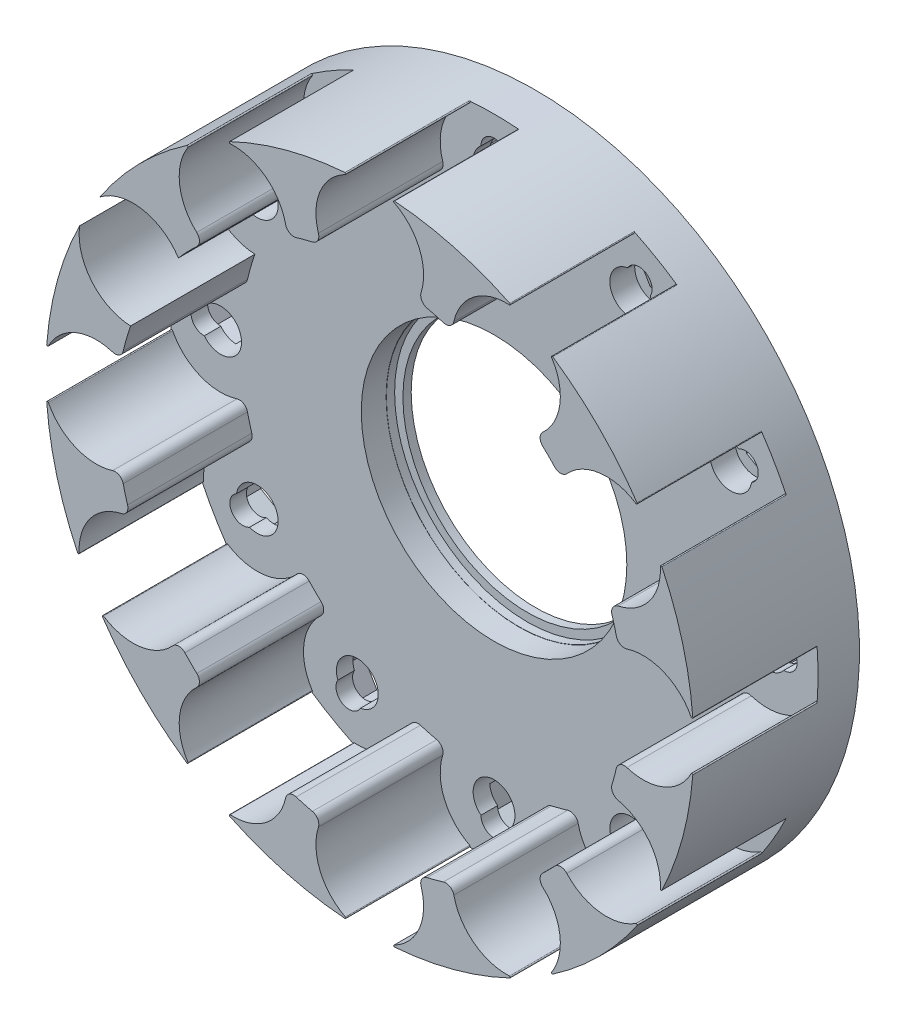
SolidWorks part; units mm, degrees
material "ABS"
ref_plane "Front Plane" through (0, 0, 0) normal (0, 0, 1) x (1, 0, 0)
ref_plane "Top Plane" through (0, 0, 0) normal (0, 1, 0) x (1, 0, 0)
ref_plane "Right Plane" through (0, 0, 0) normal (1, 0, 0) x (0, 0, -1)
sketch "Sketch1" plane through (0, 0, 0) normal (0, 0, 1) x (1, 0, 0)
  circle A0 centre (0, 0) radius 39.1
  circle A1 centre (0, 0) radius 33 construction
  circle A2 centre (33, 0) radius 2.525
  circle A3 centre (28.5788, -16.5) radius 2.525
  circle A4 centre (16.5, -28.5788) radius 2.525
  circle A5 centre (0, -33) radius 2.525
  circle A6 centre (-16.5, -28.5788) radius 2.525
  circle A7 centre (-28.5788, -16.5) radius 2.525
  circle A8 centre (-33, 0) radius 2.525
  circle A9 centre (-28.5788, 16.5) radius 2.525
  circle A10 centre (-16.5, 28.5788) radius 2.525
  circle A11 centre (0, 33) radius 2.525
  circle A12 centre (16.5, 28.5788) radius 2.525
  circle A13 centre (0, 0) radius 16.025
  circle A14 centre (28.5788, 16.5) radius 2.525
  point P28 (0, 0)
extrude "Boss-Extrude1" add sketch "Sketch1" along normal blind 3
sketch "Sketch2" plane through (0, 0, 0) normal (0, 0, -1) x (-1, 0, 0)
  circle A0 centre (0, 0) radius 16
  circle A1 centre (0, 0) radius 39.1
  circle A2 centre (0, 0) radius 39.1 construction
  dimension "D1" = 32
extrude "Boss-Extrude2" add sketch "Sketch2" along normal blind 2 contours A1 | A0
sketch "Sketch3" plane through (0, 0, 3) normal (0, 0, 1) x (1, 0, 0)
  circle A0 centre (33, 0) radius 1.6
  circle A1 centre (28.5788, -16.5) radius 1.6
  circle A2 centre (16.5, -28.5788) radius 1.6
  circle A3 centre (0, -33) radius 1.6
  circle A4 centre (-16.5, -28.5788) radius 1.6
  circle A5 centre (-28.5788, -16.5) radius 1.6
  circle A6 centre (-33, 0) radius 1.6
  circle A7 centre (-28.5788, 16.5) radius 1.6
  circle A8 centre (-16.5, 28.5788) radius 1.6
  circle A9 centre (0, 33) radius 1.6
  circle A10 centre (16.5, 28.5788) radius 1.6
  circle A11 centre (28.5788, 16.5) radius 1.6
  point P25 (0, 0)
  dimension "D1" = 3.2
  dimension "D2" = 12
sketch "Sketch4" plane through (0, 0, -2) normal (0, 0, -1) x (-1, 0, 0)
  circle A0 centre (0, 0) radius 16
  circle A1 centre (0, 0) radius 15
  dimension "D1" = 32
  dimension "D2" = 30
extrude "Boss-Extrude3" add sketch "Sketch4" against normal blind 1
sketch "Sketch5" plane through (0, 0, 3) normal (0, 0, 1) x (1, 0, 0)
  circle A0 centre (0, 0) radius 39.1
  circle A1 centre (0, 0) radius 39.1 construction
  arc A2 (-10.0063, 28.8658) -> (-19.9953, 23.0986) centre (-16.5, 28.5788) ccw
  arc A3 (5.7671, 30.0016) -> (-5.7671, 30.0016) centre (0, 33) ccw
  arc A4 (19.9953, 23.0986) -> (10.0063, 28.8658) centre (16.5, 28.5788) ccw
  arc A5 (28.8658, 10.0063) -> (23.0986, 19.9953) centre (28.5788, 16.5) ccw
  arc A6 (30.0016, -5.7671) -> (30.0016, 5.7671) centre (33, 0) ccw
  arc A7 (23.0986, -19.9953) -> (28.8658, -10.0063) centre (28.5788, -16.5) ccw
  arc A8 (10.0063, -28.8658) -> (19.9953, -23.0986) centre (16.5, -28.5788) ccw
  arc A9 (-5.7671, -30.0016) -> (5.7671, -30.0016) centre (0, -33) ccw
  arc A10 (-19.9953, -23.0986) -> (-10.0063, -28.8658) centre (-16.5, -28.5788) ccw
  arc A11 (-28.8658, -10.0063) -> (-23.0986, -19.9953) centre (-28.5788, -16.5) ccw
  arc A12 (-30.0016, 5.7671) -> (-30.0016, -5.7671) centre (-33, 0) ccw
  arc A13 (-23.0986, -19.9953) -> (-19.9953, -23.0986) centre (0, 0) ccw
  arc A14 (-30.0016, -5.7671) -> (-28.8658, -10.0063) centre (0, 0) ccw
  arc A15 (-19.9953, 23.0986) -> (-30.0016, 5.7671) centre (0, 0) ccw
  arc A16 (-5.7671, 30.0016) -> (-10.0063, 28.8658) centre (0, 0) ccw
  arc A17 (10.0063, 28.8658) -> (5.7671, 30.0016) centre (0, 0) ccw
  arc A18 (23.0986, 19.9953) -> (19.9953, 23.0986) centre (0, 0) ccw
  arc A19 (30.0016, 5.7671) -> (28.8658, 10.0063) centre (0, 0) ccw
  arc A20 (28.8658, -10.0063) -> (30.0016, -5.7671) centre (0, 0) ccw
  arc A21 (19.9953, -23.0986) -> (23.0986, -19.9953) centre (0, 0) ccw
  arc A22 (5.7671, -30.0016) -> (10.0063, -28.8658) centre (0, 0) ccw
  arc A23 (-10.0063, -28.8658) -> (-5.7671, -30.0016) centre (0, 0) ccw
  arc A24 (-23.0986, 19.9953) -> (-28.8658, 10.0063) centre (-28.5788, 16.5) ccw
  point P30 (0, 0)
  dimension "D1" = 12
  dimension "D2" = 6.5
extrude "Boss-Extrude4" add sketch "Sketch5" along normal blind 15 contours A24 A15 A2 A0 | A16 A3 A0 A2 | A17 A4 A0 A3 | A18 A5 A0 A4 | A19 A6 A0 A5 | A20 A7 A0 A6 | A21 A8 A0 A7 | A22 A9 A0 A8 | A23 A10 A0 A9 | A13 A11 A0 A10 | A14 A12 A0 A11 | A24 A0 A12 A15 region at (34.5325, 9.253, 3) region at (34.5325, -9.253, 3) region at (25.2796, 25.2796, 3) region at (25.2796, -25.2796, 3) region at (9.253, 34.5325, 3) region at (9.253, -34.5325, 3) region at (-9.253, 34.5325, 3) region at (-9.253, -34.5325, 3) region at (-25.2796, 25.2796, 3) region at (-25.2796, -25.2796, 3) region at (-34.5325, 9.253, 3) region at (-34.5325, -9.253, 3)
fillet "Fillet1" radius 0.1 22 edges at (-21.6271, 32.5742, 10.5) (-39.0236, -2.4425, 10.5) (-39.0236, 2.4425, 10.5) (-35.0167, -17.3966, 10.5) (-32.5742, -21.6271, 10.5) (-21.6271, -32.5742, 10.5) (-17.3966, -35.0167, 10.5) (-2.4425, -39.0236, 10.5) (2.4425, -39.0236, 10.5) (17.3966, -35.0167, 10.5) (21.6271, -32.5742, 10.5) (32.5742, -21.6271, 10.5) (35.0167, -17.3966, 10.5) (39.0236, -2.4425, 10.5) (39.0236, 2.4425, 10.5) (35.0167, 17.3966, 10.5) (21.6271, 32.5742, 10.5) (32.5742, 21.6271, 10.5) (17.3966, 35.0167, 10.5) (2.4425, 39.0236, 10.5) (-2.4425, 39.0236, 10.5) (-17.3966, 35.0167, 10.5)
fillet "Fillet2" radius 1 22 edges at (10.0063, -28.8658, 10.5) (5.7671, -30.0016, 10.5) (30.0016, -5.7671, 10.5) (28.8658, -10.0063, 10.5) (23.0986, -19.9953, 10.5) (19.9953, -23.0986, 10.5) (-10.0063, -28.8658, 10.5) (-5.7671, -30.0016, 10.5) (-19.9953, -23.0986, 10.5) (-23.0986, -19.9953, 10.5) (-30.0016, -5.7671, 10.5) (-28.8658, -10.0063, 10.5) (-30.0016, 5.7671, 10.5) (-19.9953, 23.0986, 10.5) (30.0016, 5.7671, 10.5) (28.8658, 10.0063, 10.5) (23.0986, 19.9953, 10.5) (19.9953, 23.0986, 10.5) (10.0063, 28.8658, 10.5) (5.7671, 30.0016, 10.5) (-5.7671, 30.0016, 10.5) (-10.0063, 28.8658, 10.5)
sketch "Sketch7" plane through (0, 0, -2) normal (0, 0, -1) x (-1, 0, 0)
  line L0 (0, 0) -> (35, 0) construction
  circle A0 centre (35, 0) radius 1.575
  circle A1 centre (30.3109, -17.5) radius 1.575
  circle A2 centre (17.5, -30.3109) radius 1.575
  circle A3 centre (0, -35) radius 1.575
  circle A4 centre (-17.5, -30.3109) radius 1.575
  circle A5 centre (-30.3109, -17.5) radius 1.575
  circle A6 centre (-35, 0) radius 1.575
  circle A7 centre (-30.3109, 17.5) radius 1.575
  circle A8 centre (-17.5, 30.3109) radius 1.575
  circle A9 centre (0, 35) radius 1.575
  circle A10 centre (17.5, 30.3109) radius 1.575
  circle A11 centre (30.3109, 17.5) radius 1.575
  point P26 (0, 0)
  dimension "D2" = 3.15
  dimension "D1" = 35
  dimension "D3" = 12
extrude "Cut-Extrude1" cut sketch "Sketch7" against normal through all
sketch "Sketch8" plane through (0, 0, -2) normal (0, 0, -1) x (-1, 0, 0)
  line L0 (33.1609, -19.1454) -> (33.1609, -15.8546)
  line L1 (38.2909, 0) -> (36.6454, 2.85)
  line L2 (36.6454, 2.85) -> (33.3546, 2.85)
  line L3 (33.3546, 2.85) -> (31.7091, 0)
  line L4 (31.7091, 0) -> (33.3546, -2.85)
  line L5 (33.3546, -2.85) -> (36.6454, -2.85)
  line L6 (36.6454, -2.85) -> (38.2909, 0)
  line L7 (33.1609, -15.8546) -> (30.3109, -14.2091)
  line L8 (30.3109, -14.2091) -> (27.4609, -15.8546)
  line L9 (27.4609, -15.8546) -> (27.4609, -19.1454)
  line L10 (27.4609, -19.1454) -> (30.3109, -20.7909)
  line L11 (30.3109, -20.7909) -> (33.1609, -19.1454)
  line L12 (19.1454, -33.1609) -> (20.7909, -30.3109)
  line L13 (20.7909, -30.3109) -> (19.1454, -27.4609)
  line L14 (19.1454, -27.4609) -> (15.8546, -27.4609)
  line L15 (15.8546, -27.4609) -> (14.2091, -30.3109)
  line L16 (14.2091, -30.3109) -> (15.8546, -33.1609)
  line L17 (15.8546, -33.1609) -> (19.1454, -33.1609)
  line L18 (0, -38.2909) -> (2.85, -36.6454)
  line L19 (2.85, -36.6454) -> (2.85, -33.3546)
  line L20 (2.85, -33.3546) -> (0, -31.7091)
  line L21 (0, -31.7091) -> (-2.85, -33.3546)
  line L22 (-2.85, -33.3546) -> (-2.85, -36.6454)
  line L23 (-2.85, -36.6454) -> (0, -38.2909)
  line L24 (-19.1454, -33.1609) -> (-15.8546, -33.1609)
  line L25 (-15.8546, -33.1609) -> (-14.2091, -30.3109)
  line L26 (-14.2091, -30.3109) -> (-15.8546, -27.4609)
  line L27 (-15.8546, -27.4609) -> (-19.1454, -27.4609)
  line L28 (-19.1454, -27.4609) -> (-20.7909, -30.3109)
  line L29 (-20.7909, -30.3109) -> (-19.1454, -33.1609)
  line L30 (-33.1609, -19.1454) -> (-30.3109, -20.7909)
  line L31 (-30.3109, -20.7909) -> (-27.4609, -19.1454)
  line L32 (-27.4609, -19.1454) -> (-27.4609, -15.8546)
  line L33 (-27.4609, -15.8546) -> (-30.3109, -14.2091)
  line L34 (-30.3109, -14.2091) -> (-33.1609, -15.8546)
  line L35 (-33.1609, -15.8546) -> (-33.1609, -19.1454)
  line L36 (-38.2909, 0) -> (-36.6454, -2.85)
  line L37 (-36.6454, -2.85) -> (-33.3546, -2.85)
  line L38 (-33.3546, -2.85) -> (-31.7091, 0)
  line L39 (-31.7091, 0) -> (-33.3546, 2.85)
  line L40 (-33.3546, 2.85) -> (-36.6454, 2.85)
  line L41 (-36.6454, 2.85) -> (-38.2909, 0)
  line L42 (-33.1609, 19.1454) -> (-33.1609, 15.8546)
  line L43 (-33.1609, 15.8546) -> (-30.3109, 14.2091)
  line L44 (-30.3109, 14.2091) -> (-27.4609, 15.8546)
  line L45 (-27.4609, 15.8546) -> (-27.4609, 19.1454)
  line L46 (-27.4609, 19.1454) -> (-30.3109, 20.7909)
  line L47 (-30.3109, 20.7909) -> (-33.1609, 19.1454)
  line L48 (-19.1454, 33.1609) -> (-20.7909, 30.3109)
  line L49 (-20.7909, 30.3109) -> (-19.1454, 27.4609)
  line L50 (-19.1454, 27.4609) -> (-15.8546, 27.4609)
  line L51 (-15.8546, 27.4609) -> (-14.2091, 30.3109)
  line L52 (-14.2091, 30.3109) -> (-15.8546, 33.1609)
  line L53 (-15.8546, 33.1609) -> (-19.1454, 33.1609)
  line L54 (0, 38.2909) -> (-2.85, 36.6454)
  line L55 (-2.85, 36.6454) -> (-2.85, 33.3546)
  line L56 (-2.85, 33.3546) -> (0, 31.7091)
  line L57 (0, 31.7091) -> (2.85, 33.3546)
  line L58 (2.85, 33.3546) -> (2.85, 36.6454)
  line L59 (2.85, 36.6454) -> (0, 38.2909)
  line L60 (19.1454, 33.1609) -> (15.8546, 33.1609)
  line L61 (15.8546, 33.1609) -> (14.2091, 30.3109)
  line L62 (14.2091, 30.3109) -> (15.8546, 27.4609)
  line L63 (15.8546, 27.4609) -> (19.1454, 27.4609)
  line L64 (19.1454, 27.4609) -> (20.7909, 30.3109)
  line L65 (20.7909, 30.3109) -> (19.1454, 33.1609)
  line L66 (33.1609, 19.1454) -> (30.3109, 20.7909)
  line L67 (30.3109, 20.7909) -> (27.4609, 19.1454)
  line L68 (27.4609, 19.1454) -> (27.4609, 15.8546)
  line L69 (27.4609, 15.8546) -> (30.3109, 14.2091)
  line L70 (30.3109, 14.2091) -> (33.1609, 15.8546)
  line L71 (33.1609, 15.8546) -> (33.1609, 19.1454)
  circle A0 centre (35, 0) radius 2.85 construction
  circle A1 centre (30.3109, -17.5) radius 2.85 construction
  circle A2 centre (17.5, -30.3109) radius 2.85 construction
  circle A3 centre (0, -35) radius 2.85 construction
  circle A4 centre (-17.5, -30.3109) radius 2.85 construction
  circle A5 centre (-30.3109, -17.5) radius 2.85 construction
  circle A6 centre (-35, 0) radius 2.85 construction
  circle A7 centre (-30.3109, 17.5) radius 2.85 construction
  circle A8 centre (-17.5, 30.3109) radius 2.85 construction
  circle A9 centre (0, 35) radius 2.85 construction
  circle A10 centre (17.5, 30.3109) radius 2.85 construction
  circle A11 centre (30.3109, 17.5) radius 2.85 construction
  point P91 (0, 0)
  dimension "D1" = 5.7
  dimension "D2" = 12
extrude "Cut-Extrude3" cut sketch "Sketch8" against normal blind 3
equation "\"RingPinShaft\"= 5.05"
equation "\"CenterBearingOut\"=32.05"
equation "\"OutputBearingOut\"=37.05"
equation "\"RingPostIn\"=5.15"
equation "\"CamBearingOut\"=15.1"
equation "\"DiskOutputShaft\"=10.1"
equation "\"CenterShaft\"=25.2"
equation "\"Eccentricity\"=2"
equation "\"CycCamShaft\"=10.05"
equation "\"m3Thru\"=3.15"
equation "\"m3Insert\"=4.2"
equation "\"MountingHoleDiam\"=35"
equation "\"D1@Sketch7\"=\"MountingHoleDiam\""
equation "\"D2@Sketch7\"=\"m3Thru\""
